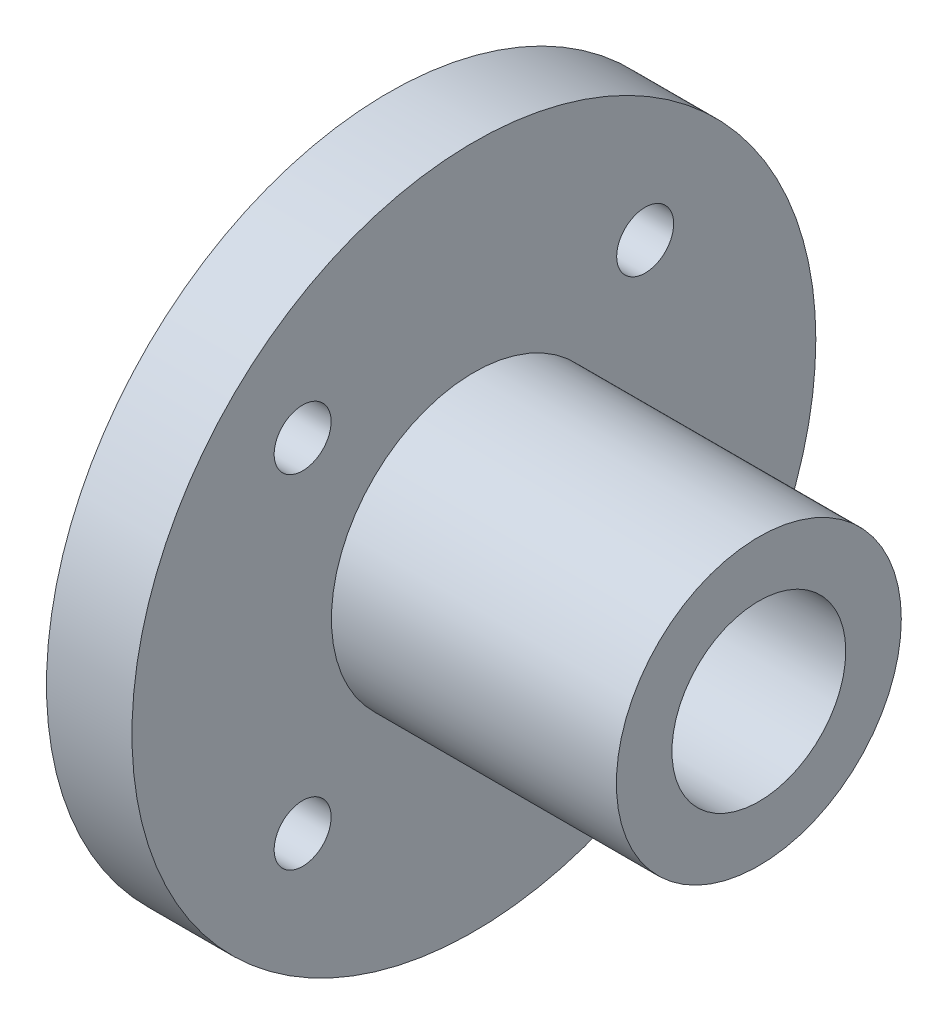
SolidWorks part; units mm, degrees
note: The reader was unsure of these and kept them because the rebuilt part matched: shared geometry of "Sketch1<3>".
ref_plane "Front Plane" through (0, 0, 0) normal (0, 0, 1) x (1, 0, 0)
ref_plane "Top Plane" through (0, 0, 0) normal (0, 1, 0) x (1, 0, 0)
ref_plane "Right Plane" through (0, 0, 0) normal (1, 0, 0) x (0, 0, -1)
sketch "Sketch1" plane through (0, 0, 0) normal (1, 0, 0) x (0, 0, -1)
  circle A0 centre (0, 0) radius 12
  circle A1 centre (0, 0) radius 3.05
  circle A2 centre (0, 0) radius 5
  dimension "D1" = 24
  dimension "D2" = 6.1
  dimension "D3" = 10
extrude "Boss-Extrude1" add sketch "Sketch1" against normal blind 3 contours A0 A2 | A2 A1 | A1
extrude "Boss-Extrude2" add sketch "Sketch1<3>" along normal blind 10 contours A2 A1
sketch "Sketch1<3>" plane through (0, 0, 0) normal (1, 0, 0) x (0, 0, -1) same geometry as "Sketch1"
sketch "Sketch2" plane through (-3, 0, 0) normal (-1, 0, 0) x (0, 0, 1)
  line L0 (-12.0208, 0) -> (0, 12.0208) construction
  line L1 (-12.0208, 0) -> (0, -12.0208) construction
  line L2 (0, 12.0208) -> (12.0208, 0) construction
  line L3 (0, -12.0208) -> (12.0208, 0) construction
  line L4 (-12.0208, 0) -> (12.0208, 0) construction
  line L5 (0, 12.0208) -> (0, -12.0208) construction
  circle A0 centre (-6.0104, 6.0104) radius 1
  circle A1 centre (-6.0104, -6.0104) radius 1
  circle A2 centre (6.0104, 6.0104) radius 1
  circle A3 centre (6.0104, -6.0104) radius 1
  point P1 (0, 0)
  dimension "D2" = 2
  dimension "D1" = 17
extrude "Cut-Extrude1" cut sketch "Sketch2" against normal blind 10
